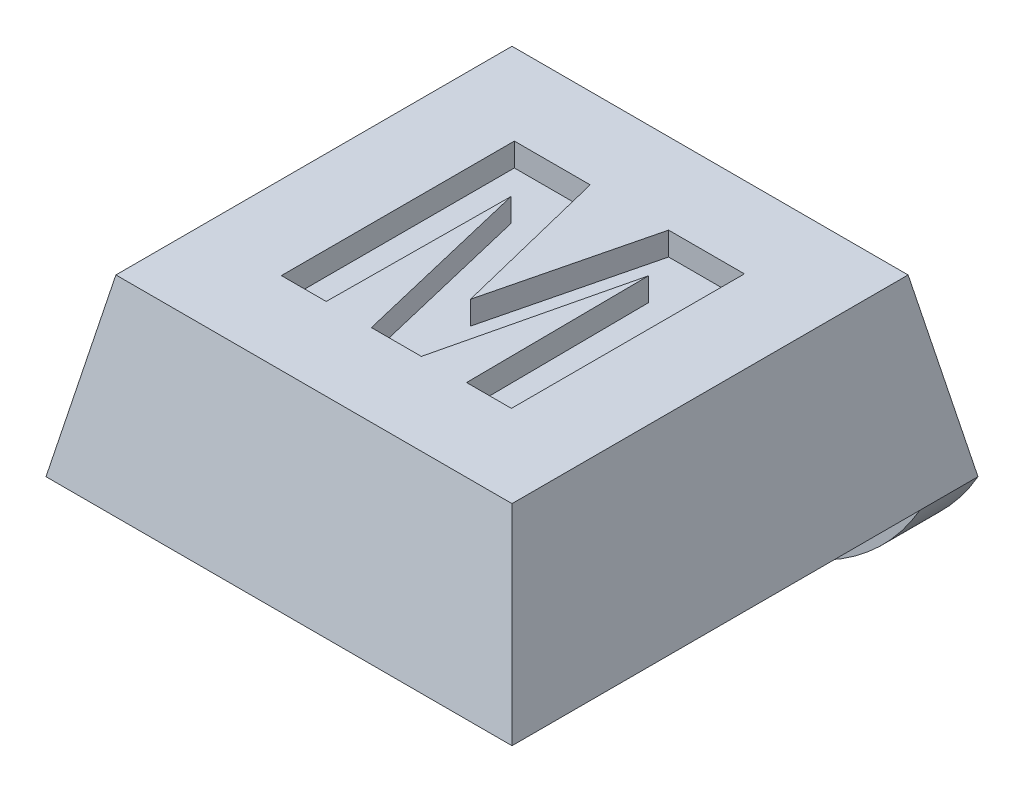
SolidWorks part; units mm, degrees
ref_plane "Front Plane" through (0, 0, 0) normal (0, 0, 1) x (1, 0, 0)
ref_plane "Top Plane" through (0, 0, 0) normal (0, 1, 0) x (1, 0, 0)
ref_plane "Right Plane" through (0, 0, 0) normal (1, 0, 0) x (0, 0, -1)
sketch "Sketch1" plane through (0, 0, 0) normal (0, 1, 0) x (1, 0, 0)
  line L1 (0, 0) -> (8, 0)
  line L2 (0, 0) -> (0, 8)
  line L3 (0, 8) -> (8, 8)
  line L4 (8, 0) -> (8, 8)
  dimension "D1" = 8
  dimension "D2" = 8
extrude "Boss-Extrude1" add sketch "Sketch1" along normal blind 3
sketch "Sketch2" plane through (0, 0, 0) normal (0, 0, 1) x (1, 0, 0)
  line L0 (0, 0) -> (0.6, 3)
  line L1 (0, 3) -> (8, 3) construction
  line L2 (0.6, 3) -> (0, 3)
  line L3 (0, 3) -> (0, 0)
  line L4 (8, 0) -> (7.4, 3)
  line L5 (7.4, 3) -> (8, 3)
  line L6 (8, 3) -> (8, 0)
  dimension "D1" = 0.6
  dimension "D2" = 0.6
extrude "Cut-Extrude1" cut sketch "Sketch2" against normal through all both and the other way through all
sketch "Sketch3" plane through (0, 0, 0) normal (1, 0, 0) x (0, 0, -1)
  line L0 (0, 0) -> (0.6, 3)
  line L1 (8, 3) -> (0, 3) construction
  line L2 (0.6, 3) -> (0, 3)
  line L3 (0, 3) -> (0, 0)
  line L4 (8, 3) -> (7.4, 3)
  line L5 (7.4, 3) -> (8, 0)
  line L6 (8, 3) -> (8, 0)
  dimension "D1" = 0.6
  dimension "D2" = 0.6
extrude "Cut-Extrude2" cut sketch "Sketch3" along normal blind 11
sketch "Sketch4" plane through (0, 0, 0) normal (0, -1, 0) x (1, 0, 0)
  line L0 (8, 0) -> (8, -8) construction
  line L3 (0, 0) -> (8, 0) construction
  circle A0 centre (4, -3.75) radius 1.8
  dimension "D1" = 3.6
  dimension "D2" = 4
  dimension "D3" = 3.75
extrude "Cut-Extrude3" cut sketch "Sketch4" against normal blind 0.8
sketch "Sketch5" plane through (0, 0, 0) normal (0, -1, 0) x (1, 0, 0)
  line L0 (8, 0) -> (8, -8) construction
  line L1 (0, -8) -> (8, -8)
  line L2 (0, -8) -> (0, -7)
  line L3 (0, -7) -> (8, -7)
  line L4 (8, -8) -> (8, -7)
  dimension "D1" = 1
extrude "Boss-Extrude2" add sketch "Sketch5" along normal blind 2
fillet "Fillet1" radius 4 2 edges at (8, -2, -7.5) (0, -2, -7.5)
sketch "Sketch6" plane through (0, 3, 0) normal (0, 1, 0) x (1, 0, 0)
  text T0 "M" font "Arial" height 4
extrude "Cut-Extrude4" cut sketch "Sketch6" against normal blind 0.4
